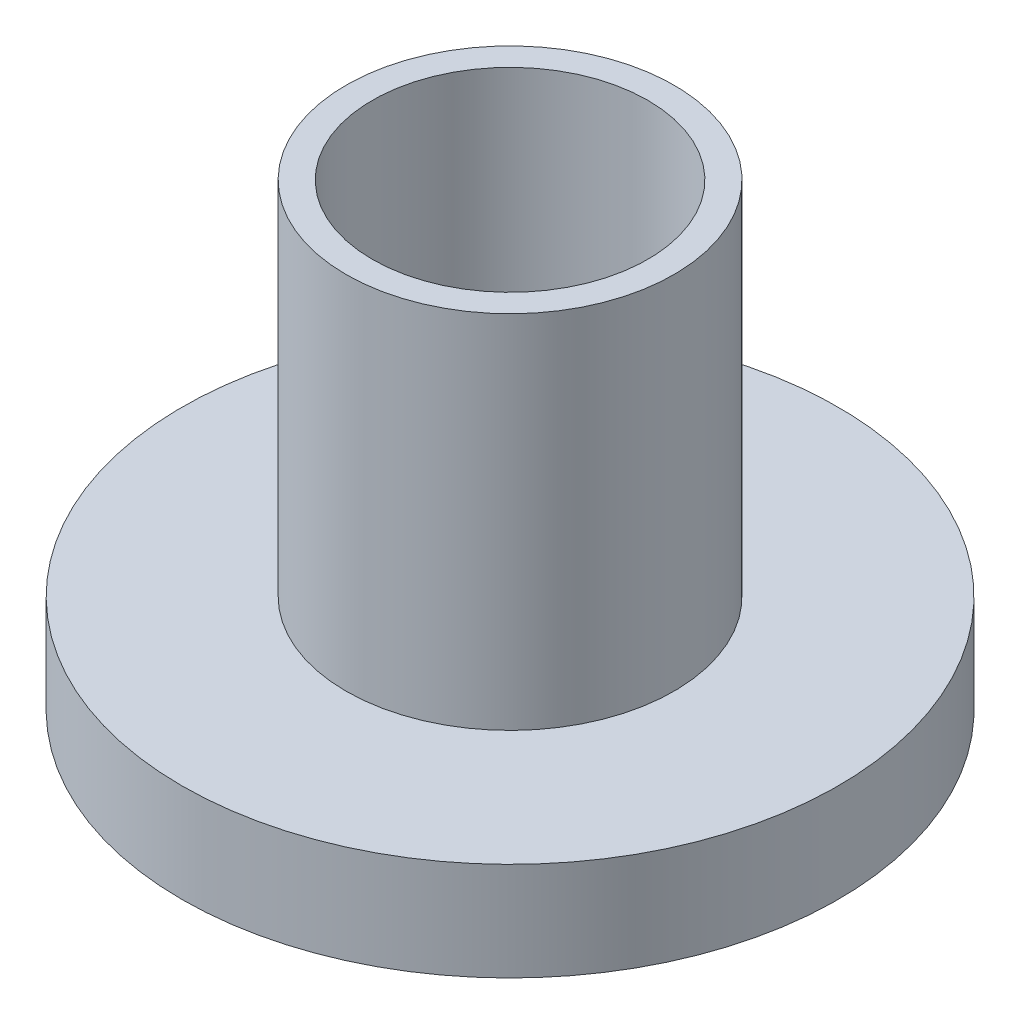
SolidWorks part; units mm, degrees
ref_plane "前视基准面" through (0, 0, 0) normal (0, 0, 1) x (1, 0, 0)
ref_plane "上视基准面" through (0, 0, 0) normal (0, 1, 0) x (1, 0, 0)
ref_plane "右视基准面" through (0, 0, 0) normal (1, 0, 0) x (0, 0, -1)
sketch "草图1" plane through (0, 0, 0) normal (0, 1, 0) x (1, 0, 0)
  circle A0 centre (0, 0) radius 2.5
  circle A1 centre (0, 0) radius 2.1
  circle A2 centre (0, 0) radius 5
  dimension "D1" = 4.2
  dimension "D2" = 5
  dimension "D3" = 10
extrude "凸台-拉伸1" add sketch "草图1" along normal blind 5.5 contours A0 A1 region at (-2.4293, 0, 0)
extrude "凸台-拉伸2" add sketch "草图1<3>" against normal blind 1.5 contours A2 A0 | A0 A1 region at (-2.4293, 0, 0) region at (-4.8586, 0, 0)
sketch "草图1<3>" plane through (0, 0, 0) normal (0, 1, 0) x (1, 0, 0) same geometry as "草图1"
